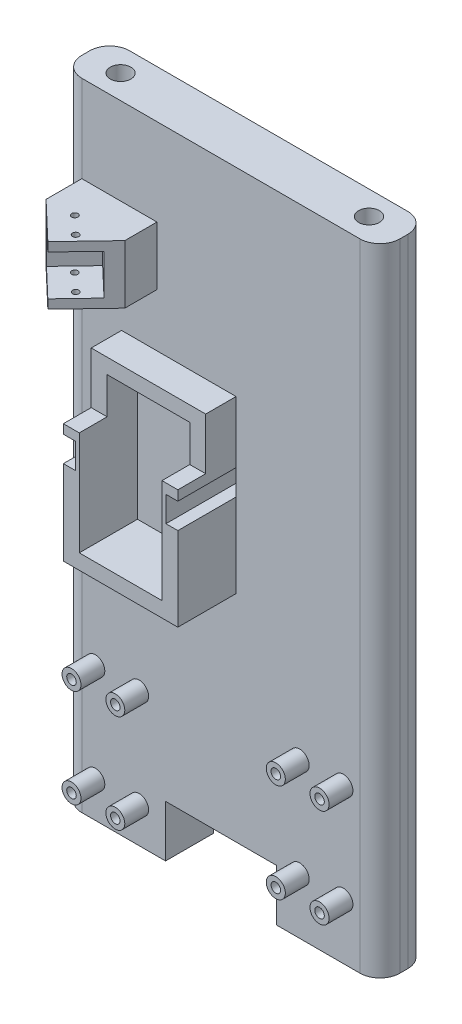
SolidWorks part; units mm, degrees
ref_plane "Front Plane" through (0, 0, 0) normal (0, 0, 1) x (1, 0, 0)
ref_plane "Top Plane" through (0, 0, 0) normal (0, 1, 0) x (1, 0, 0)
ref_plane "Right Plane" through (0, 0, 0) normal (1, 0, 0) x (0, 0, -1)
sketch "Sketch1" plane through (0, 0, 0) normal (0, 0, 1) x (1, 0, 0)
  line L1 (0, 0) -> (101.6, 0)
  line L2 (0, 0) -> (0, 203.2)
  line L3 (0, 203.2) -> (101.6, 203.2)
  line L4 (101.6, 0) -> (101.6, 203.2)
  dimension "D1" = 101.6
  dimension "D2" = 203.2
extrude "Boss-Extrude1" add sketch "Sketch1" along normal mid plane 15.24
fillet "Fillet1" radius 6.35 1 edges at (101.6, 101.6, 7.62)
fillet "Fillet2" radius 6.35 1 edges at (101.6, 101.6, -7.62)
fillet "Fillet3" radius 6.35 1 edges at (0, 101.6, -7.62)
fillet "Fillet4" radius 6.35 1 edges at (0, 101.6, 7.62)
sketch "Sketch2" plane through (0, 203.2, 0) normal (0, 1, 0) x (1, 0, 0)
  circle A0 centre (11.1125, 0) radius 3.302
  circle A1 centre (90.4875, 0) radius 3.302
  dimension "D1" = 79.375
  dimension "D2" = 6.604
  dimension "D3" = 11.1125
extrude "Cut-Extrude1" cut sketch "Sketch2" against normal through all
sketch "Sketch4" plane through (0, 0, 7.62) normal (0, 0, 1) x (1, 0, 0)
  line L0 (6.35, 203.2) -> (6.35, 0) construction
  line L1 (6.35, 175.418) -> (30.35, 175.418)
  line L2 (6.35, 175.418) -> (6.35, 156.718)
  line L3 (6.35, 156.718) -> (30.35, 156.718)
  line L4 (30.35, 175.418) -> (30.35, 156.718)
  line L5 (95.25, 0) -> (95.25, 203.2) construction
  line L6 (95.25, 109.0676) -> (71.7296, 109.0676)
  line L7 (95.25, 109.0676) -> (95.25, 7.62)
  line L8 (95.25, 7.62) -> (71.7296, 7.62)
  line L9 (71.7296, 109.0676) -> (71.7296, 7.62)
  line L10 (6.35, 0) -> (95.25, 0) construction
  line L11 (6.35, 7.62) -> (29.083, 7.62)
  line L12 (6.35, 7.62) -> (6.35, 47.1424)
  line L13 (6.35, 47.1424) -> (29.083, 47.1424)
  line L14 (29.083, 7.62) -> (29.083, 47.1424)
  line L15 (19.05, 139.7762) -> (55.626, 139.7762)
  line L16 (19.05, 139.7762) -> (19.05, 85.2424)
  line L17 (19.05, 85.2424) -> (55.626, 85.2424)
  line L18 (55.626, 139.7762) -> (55.626, 85.2424)
  line L25 (95.25, 203.2) -> (6.35, 203.2) construction
  line L26 (33.1089, 0) -> (68.4911, 0)
  line L27 (33.1089, 0) -> (33.1089, 16.5016)
  line L28 (24.13, 134.9502) -> (50.546, 134.9502)
  line L29 (24.13, 134.9502) -> (24.13, 90.0684)
  line L30 (24.13, 90.0684) -> (50.546, 90.0684)
  line L31 (50.546, 134.9502) -> (50.546, 90.0684)
  line L32 (33.1089, 16.5016) -> (68.4911, 16.5016)
  line L33 (68.4911, 0) -> (68.4911, 16.5016)
  point P24 (50.8254, 6.35)
  point P27 (50.8, 16.5016)
  point P36 (50.8, 203.2)
  dimension "D1" = 24
  dimension "D2" = 18.7
  dimension "D3" = 101.4476
  dimension "D4" = 23.5204
  dimension "D5" = 22.733
  dimension "D6" = 39.5224
  dimension "D7" = 36.576
  dimension "D8" = 54.5338
  dimension "D9" = 7.62
  dimension "D10" = 35.3821
  dimension "D11" = 12.7
  dimension "D12" = 38.1
  dimension "D13" = 16.5016
  dimension "D14" = 44.4754
  dimension "D15" = 196.85
  dimension "D16" = 4.826
  dimension "D17" = 4.826
  dimension "D18" = 5.08
  dimension "D19" = 5.08
  dimension "D20" = 156.718
sketch "Sketch5" plane through (0, 0, 7.62) normal (0, 0, 1) x (1, 0, 0)
  line L1 (19.05, 139.7762) -> (55.626, 139.7762)
  line L2 (19.05, 139.7762) -> (19.05, 85.2424)
  line L3 (19.05, 85.2424) -> (55.626, 85.2424)
  line L4 (55.626, 139.7762) -> (55.626, 85.2424)
  line L5 (24.13, 134.9502) -> (50.546, 134.9502)
  line L6 (24.13, 134.9502) -> (24.13, 90.0684)
  line L7 (24.13, 90.0684) -> (50.546, 90.0684)
  line L8 (50.546, 134.9502) -> (50.546, 90.0684)
extrude "Boss-Extrude2" add sketch "Sketch5" along normal blind 18.5928 contours L2 L1 L4 L3 | L6 L5 L8 L7
sketch "Sketch7" plane through (0, 0, 7.62) normal (0, 0, 1) x (1, 0, 0)
  line L0 (6.35, 203.2) -> (6.35, 0) construction
  line L1 (6.35, 175.418) -> (30.35, 175.418)
  line L2 (6.35, 175.418) -> (6.35, 156.718)
  line L3 (6.35, 156.718) -> (30.35, 156.718)
  line L4 (30.35, 175.418) -> (30.35, 156.718)
  line L5 (6.35, 0) -> (95.25, 0) construction
  dimension "D1" = 18.7
  dimension "D2" = 24
  dimension "D3" = 156.718
extrude "Boss-Extrude3" add sketch "Sketch7" along normal blind 22.86
sketch "Sketch9" plane through (0, 0, 7.62) normal (0, 0, 1) x (1, 0, 0)
  line L0 (55.626, 139.7762) -> (55.626, 85.2424) construction
  line L1 (55.626, 120.1025) -> (51.816, 120.1025)
  line L2 (55.626, 120.1025) -> (55.626, 111.9745)
  line L3 (55.626, 111.9745) -> (51.816, 111.9745)
  line L4 (51.816, 120.1025) -> (51.816, 111.9745)
  line L5 (19.05, 139.7762) -> (19.05, 85.2424) construction
  line L6 (19.05, 120.3474) -> (22.86, 120.3474)
  line L7 (19.05, 120.3474) -> (19.05, 112.2194)
  line L8 (19.05, 112.2194) -> (22.86, 112.2194)
  line L9 (22.86, 120.3474) -> (22.86, 112.2194)
  line L10 (6.35, 156.718) -> (6.35, 0) construction
  line L11 (6.35, 156.718) -> (30.35, 156.718) construction
  dimension "D1" = 3.81
  dimension "D2" = 8.128
  dimension "D3" = 36.3706
  dimension "D4" = 36.6155
extrude "Cut-Extrude3" cut sketch "Sketch9" against normal through all both and the other way through all
ref_plane "Plane1" through (55.626, 0, 0) normal (1, 0, 0) x (0, 0, -1)
sketch "Sketch23" plane through (55.626, 0, 0) normal (1, 0, 0) x (0, 0, -1)
  line L1 (-26.2128, 139.7762) -> (-17.3228, 139.7762)
  line L2 (-26.2128, 139.7762) -> (-26.2128, 123.2662)
  line L3 (-26.2128, 123.2662) -> (-17.3228, 123.2662)
  line L4 (-17.3228, 139.7762) -> (-17.3228, 123.2662)
  dimension "D1" = 8.89
  dimension "D2" = 16.51
extrude "Cut-Extrude9" cut sketch "Sketch23" against normal through all
ref_plane "Plane2" through (0, 175.418, 0) normal (0, 1, 0) x (1, 0, 0)
sketch "Sketch12" plane through (0, 175.418, 0) normal (0, 1, 0) x (1, 0, 0)
  line L0 (6.35, -19.05) -> (18.35, -30.48)
  line L1 (6.35, -30.48) -> (6.35, -7.62) construction
  line L2 (30.35, -30.48) -> (6.35, -30.48) construction
  line L3 (18.35, -30.48) -> (30.35, -17.8816)
  line L4 (30.35, -30.48) -> (30.35, -7.62) construction
  line L5 (6.35, -19.05) -> (6.35, -30.48)
  line L6 (6.35, -30.48) -> (30.35, -30.48)
  line L7 (30.35, -30.48) -> (30.35, -17.8816)
extrude "Cut-Extrude5" cut sketch "Sketch12" against normal blind 20.574 contours L5 L6 L0 | L6 L7 L3 region at (26.35, 175.418, 26.2805) region at (10.35, 175.418, 26.67)
ref_plane "Plane3" through (0, 166.068, 0) normal (0, -1, 0) x (-1, 0, 0)
sketch "Sketch13" plane through (0, 166.068, 0) normal (0, -1, 0) x (-1, 0, 0)
  line L10 (-18.35, -30.48) -> (-27.1092, -21.284)
  line L11 (-18.35, -30.48) -> (-30.35, -17.8816) construction
  line L13 (-27.1092, -21.284) -> (-17.9132, -12.5248)
  line L14 (-17.9132, -12.5248) -> (-9.154, -21.7208)
  line L15 (-6.35, -19.05) -> (-18.35, -30.48) construction
  line L16 (-9.154, -21.7208) -> (-18.35, -30.48)
  dimension "D1" = 12.7
  dimension "D2" = 12.7
extrude "Cut-Extrude6" cut sketch "Sketch13" against normal mid plane 12.954
sketch "Sketch14" plane through (0, 0, 7.62) normal (0, 0, 1) x (1, 0, 0)
  line L0 (6.35, 7.62) -> (6.35, 47.1424) construction
  circle A0 centre (10.668, 42.83) radius 1.524
  circle A1 centre (24.668, 42.83) radius 1.524
  circle A2 centre (10.668, 11.43) radius 1.524
  circle A3 centre (24.668, 11.43) radius 1.524
  circle A4 centre (10.668, 42.83) radius 3.0226
  circle A5 centre (24.668, 42.83) radius 3.0226
  circle A6 centre (24.668, 11.43) radius 3.0226
  circle A7 centre (10.668, 11.43) radius 3.0226
  dimension "D1" = 3.048
  dimension "D2" = 14
  dimension "D6" = 6.0452
  dimension "D3" = 31.4
  dimension "D4" = 4.318
  dimension "D5" = 3.81
extrude "Boss-Extrude4" add sketch "Sketch14" along normal blind 7.62
sketch "Sketch16" plane through (0, 0, 7.62) normal (0, 0, 1) x (1, 0, 0)
  line L0 (55.626, 139.7762) -> (55.626, 120.1025) construction
  line L1 (19.05, 139.7762) -> (55.626, 139.7762) construction
  circle A0 centre (75.946, 17.8562) radius 1.524
  circle A1 centre (89.916, 17.8562) radius 1.524
  circle A2 centre (89.916, 49.3522) radius 1.524
  circle A3 centre (75.946, 49.3522) radius 1.524
  circle A4 centre (75.946, 49.3522) radius 3.048
  circle A5 centre (89.916, 49.3522) radius 3.048
  circle A6 centre (75.946, 17.8562) radius 3.048
  circle A7 centre (89.916, 17.8562) radius 3.048
  dimension "D1" = 3.048
  dimension "D6" = 121.92
  dimension "D2" = 6.096
  dimension "D3" = 20.32
  dimension "D4" = 13.97
  dimension "D5" = 31.496
extrude "Boss-Extrude5" add sketch "Sketch16" along normal blind 7.62
sketch "Sketch18" plane through (0, 175.418, 0) normal (0, 1, 0) x (1, 0, 0)
  line L0 (18.35, -30.48) -> (27.1092, -21.284)
  line L1 (18.35, -30.48) -> (30.35, -17.8816) construction
  line L2 (27.1092, -21.284) -> (17.9132, -12.5248)
  line L3 (17.9132, -12.5248) -> (9.154, -21.7208)
  line L4 (13.1346, -16.7428) -> (22.3306, -25.502) construction
  line L5 (9.154, -21.7208) -> (18.35, -30.48)
  line L6 (6.35, -19.05) -> (18.35, -30.48) construction
  circle A0 centre (15.3728, -18.8746) radius 1
  circle A1 centre (20.8904, -24.1302) radius 1
  dimension "D3" = 2
  dimension "D1" = 12.7
  dimension "D2" = 12.7
  dimension "D4" = 7.62
  dimension "D5" = 2.54
  dimension "D6" = 6.35
extrude "Cut-Extrude7" cut sketch "Sketch18" against normal blind 18.7 contours L4 A1 | A1 L4 | A0 region at (21.1831, 175.418, 23.8228) region at (20.5977, 175.418, 24.4375)
sketch "Sketch22" plane through (0, 0, 7.62) normal (0, 0, 1) x (1, 0, 0)
  line L1 (33.1089, 0) -> (68.4911, 0)
  line L2 (33.1089, 0) -> (33.1089, 16.5016)
  line L3 (33.1089, 16.5016) -> (68.4911, 16.5016)
  line L4 (68.4911, 0) -> (68.4911, 16.5016)
extrude "Cut-Extrude8" cut sketch "Sketch22" against normal through all
